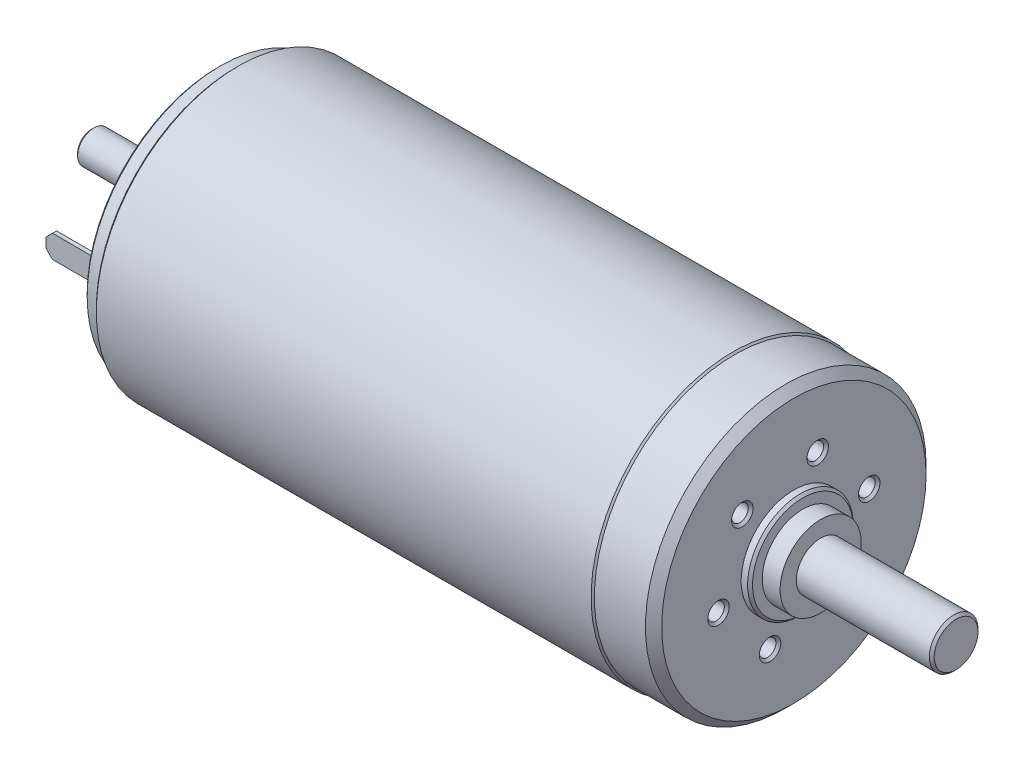
SolidWorks part; units mm, degrees
ref_plane "Front Plane" through (0, 0, 0) normal (0, 0, 1) x (1, 0, 0)
ref_plane "Top Plane" through (0, 0, 0) normal (0, 1, 0) x (1, 0, 0)
ref_plane "Right Plane" through (0, 0, 0) normal (1, 0, 0) x (0, 0, -1)
sketch "Sketch1" plane through (0, 0, 0) normal (1, 0, 0) x (0, 0, -1)
  circle A0 centre (0, 0) radius 17.5
  circle A1 centre (0, 0) radius 3 construction
  circle A2 centre (0, 0) radius 6.5 construction
  circle A3 centre (0, 0) radius 2 construction
  circle A4 centre (0, 0) radius 16.425 construction
  circle A5 centre (0, 0) radius 5 construction
extrude "Boss-Extrude1" add sketch "Sketch1" against normal blind 61.5
sketch "Sketch3" plane through (0, 0, 0) normal (1, 0, 0) x (0, 0, -1)
  circle A0 centre (0, 0) radius 17.3
extrude "Boss-Extrude2" add sketch "Sketch3" along normal blind 7.3
sketch "Sketch4" plane through (7.3, 0, 0) normal (1, 0, 0) x (0, 0, -1)
  circle A0 centre (0, 0) radius 6.5
extrude "Boss-Extrude3" add sketch "Sketch4" along normal blind 1.1
sketch "Sketch5" plane through (8.4, 0, 0) normal (1, 0, 0) x (0, 0, -1)
  circle A0 centre (0, 0) radius 5
extrude "Boss-Extrude4" add sketch "Sketch5" along normal blind 2.2
sketch "Sketch6" plane through (10.6, 0, 0) normal (1, 0, 0) x (0, 0, -1)
  circle A0 centre (0, 0) radius 3
extrude "Boss-Extrude5" add sketch "Sketch6" along normal blind 16.7
sketch "Sketch7" plane through (-61.5, 0, 0) normal (-1, 0, 0) x (0, 0, 1)
  circle A0 centre (0, 0) radius 16.425
extrude "Boss-Extrude6" add sketch "Sketch7" along normal blind 2.2
sketch "Sketch8" plane through (-63.7, 0, 0) normal (-1, 0, 0) x (0, 0, 1)
  circle A0 centre (0, 0) radius 6.5
extrude "Boss-Extrude7" add sketch "Sketch8" along normal blind 1.35
sketch "Sketch9" plane through (-65.05, 0, 0) normal (-1, 0, 0) x (0, 0, 1)
  circle A0 centre (0, 0) radius 3.5
extrude "Boss-Extrude8" add sketch "Sketch9" along normal blind 2.05
sketch "Sketch10" plane through (-67.1, 0, 0) normal (-1, 0, 0) x (0, 0, 1)
  circle A0 centre (0, 0) radius 2
extrude "Boss-Extrude9" add sketch "Sketch10" along normal blind 12.2
sketch "Sketch11" plane through (-63.7, 0, 0) normal (-1, 0, 0) x (0, 0, 1)
  line L0 (-12.7, 1.4) -> (-13.2, 1.4)
  line L1 (-13.2, 1.4) -> (-13.2, 0)
  line L2 (-13.2, 0) -> (-13.2, -1.4)
  line L3 (-13.2, -1.4) -> (-12.7, -1.4)
  line L4 (-12.7, -1.4) -> (-12.7, 0)
  line L5 (-12.7, 0) -> (-12.7, 1.4)
  line L6 (12.7, -1.4) -> (13.2, -1.4)
  line L7 (13.2, -1.4) -> (13.2, 0)
  line L8 (13.2, 0) -> (13.2, 1.4)
  line L9 (13.2, 1.4) -> (12.7, 1.4)
  line L10 (12.7, 1.4) -> (12.7, 0)
  line L11 (12.7, 0) -> (12.7, -1.4)
  circle A0 centre (0, 0) radius 12.7 construction
  point P3 (-12.7, 0)
  point P4 (12.7, 0)
  point P5 (12.7, 1.4)
  point P6 (12.7, -1.4)
  point P7 (-12.7, 1.4)
  point P8 (-12.7, -1.4)
  point P9 (13.2, -1.4)
  point P10 (13.2, 1.4)
  point P11 (13.2, 0)
  point P12 (-13.2, -1.4)
  point P13 (-13.2, 1.4)
  point P14 (-13.2, 0)
extrude "Boss-Extrude10" add sketch "Sketch11" along normal blind 8
chamfer "Chamfer1" distance 0.3 angle 45 6 edges at (-79.3, 0, 2) (27.3, 0, -3) (8.4, 0, -6.5) (-65.05, 0, 6.5) (-63.7, 0, 16.425) (-61.5, 0, -17.5)
chamfer "Chamfer2" distance 0.2 angle 45 1 edges at (0, 0, -17.5)
chamfer "Chamfer3" distance 1 angle 45 1 edges at (7.3, 0, -17.3)
chamfer "Chamfer4" distance 0.8 angle 45 4 edges at (-71.7, -1.4, -12.95) (-71.7, 1.4, -12.95) (-71.7, -1.4, 12.95) (-71.7, 1.4, 12.95)
sketch "Sketch12" plane through (7.3, 0, 0) normal (1, 0, 0) x (0, 0, -1)
  line L1 (2.9357, 9.035) -> (-6.3567, 7.0599) construction
  line L2 (-6.3567, 7.0599) -> (-9.2924, -1.9752) construction
  line L3 (-9.2924, -1.9752) -> (-2.9357, -9.035) construction
  line L4 (-2.9357, -9.035) -> (6.3567, -7.0599) construction
  line L5 (6.3567, -7.0599) -> (9.2924, 1.9752) construction
  line L6 (9.2924, 1.9752) -> (2.9357, 9.035) construction
  circle A1 centre (0, 0) radius 9.5 construction
hole_wizard "M2.5x0.45 Tapped Hole1" positions "Sketch14" profile "Sketch13" tap size "M2.5x0.45" standard "ANSI Metric"
sketch "Sketch14" plane through (7.3, 0, 0) normal (1, 0, 0) x (0, 0, -1)
  point P0 (-6.3567, 7.0599)
  point P3 (2.9357, 9.035)
  point P6 (9.2924, 1.9752)
  point P9 (6.3567, -7.0599)
  point P12 (-2.9357, -9.035)
  point P15 (-9.2924, -1.9752)
sketch "Sketch13" plane through (7.3, 7.0599, 6.3567) normal (0, 1, 0) x (0, 0, -1)
  line L0 (0, 0) -> (0, 5.1159)
  line L1 (0, 5.1159) -> (1.025, 4.5)
  line L2 (1.025, 4.5) -> (1.025, 0.3)
  line L3 (1.025, 0.3) -> (1.325, 0)
  line L5 (1.325, 0) -> (0, 0)
  line L6 (-1.025, 0.3) -> (-1.325, 0) construction
  line L10 (0, 5.1159) -> (-1.025, 4.5) construction
  line L11 (0, -6.35) -> (0, 107.95) construction
  dimension "Tap Drill Dia." = 2.05
  dimension "Tap Drill Depth" = 4.5
  dimension "Near C'Sink Dia." = 2.65
  dimension "Near C'Sink Angle" = 90
  dimension "Drill Angle" = 118
sketch "Sketch15" plane through (-63.7, 0, 0) normal (-1, 0, 0) x (0, 0, 1)
  line L0 (0, 0) -> (8.6193, 11.0322) construction
  line L1 (0, 0) -> (-8.6193, -11.0322) construction
  line L2 (0, 0) -> (-5.2445, 12.9806) construction
  line L3 (0, 0) -> (5.2445, -12.9806) construction
  line L4 (0, 0) -> (10.886, 6.541) construction
  line L5 (0, 0) -> (-10.886, -6.541) construction
  line L6 (0, 0) -> (-6.541, 10.886) construction
  line L7 (0, 0) -> (6.541, -10.886) construction
  circle A0 centre (0, 0) radius 14 construction
  circle A1 centre (0, 0) radius 12.7 construction
hole_wizard "M2x0.4 Tapped Hole1" positions "Sketch17" profile "Sketch16" tap size "M2x0.4" standard "ANSI Metric"
sketch "Sketch17" plane through (-63.7, 0, 0) normal (-1, 0, 0) x (0, 0, 1)
  point P0 (8.6193, 11.0322)
  point P3 (-5.2445, 12.9806)
  point P6 (-8.6193, -11.0322)
  point P9 (5.2445, -12.9806)
sketch "Sketch16" plane through (-63.7, 11.0322, 8.6193) normal (0, 1, 0) x (0, 0, 1)
  line L0 (0, 0) -> (0, 3.4807)
  line L1 (0, 3.4807) -> (0.8, 3)
  line L2 (0.8, 3) -> (0.8, 0.25)
  line L3 (0.8, 0.25) -> (1.05, 0)
  line L5 (1.05, 0) -> (0, 0)
  line L6 (-0.8, 0.25) -> (-1.05, 0) construction
  line L10 (0, 3.4807) -> (-0.8, 3) construction
  line L11 (0, -6.35) -> (0, 107.95) construction
  dimension "Tap Drill Dia." = 1.6
  dimension "Tap Drill Depth" = 3
  dimension "Near C'Sink Dia." = 2.1
  dimension "Near C'Sink Angle" = 90
  dimension "Drill Angle" = 118
hole_wizard "M1.6x0.35 Tapped Hole1" positions "Sketch19" profile "Sketch18" tap size "M1.6x0.35" standard "ANSI Metric"
sketch "Sketch19" plane through (-63.7, 0, 0) normal (-1, 0, 0) x (0, 0, 1)
  point P0 (-6.541, 10.886)
  point P3 (-10.886, -6.541)
  point P6 (6.541, -10.886)
  point P9 (10.886, 6.541)
sketch "Sketch18" plane through (-63.7, 10.886, -6.541) normal (0, 1, 0) x (0, 0, 1)
  line L0 (0, 0) -> (0, 5.3255)
  line L1 (0, 5.3255) -> (0.625, 4.95)
  line L2 (0.625, 4.95) -> (0.625, 0.225)
  line L3 (0.625, 0.225) -> (0.85, 0)
  line L5 (0.85, 0) -> (0, 0)
  line L6 (-0.625, 0.225) -> (-0.85, 0) construction
  line L10 (0, 5.3255) -> (-0.625, 4.95) construction
  line L11 (0, -6.35) -> (0, 107.95) construction
  dimension "Tap Drill Dia." = 1.25
  dimension "Tap Drill Depth" = 4.95
  dimension "Near C'Sink Dia." = 1.7
  dimension "Near C'Sink Angle" = 90
  dimension "Drill Angle" = 118
